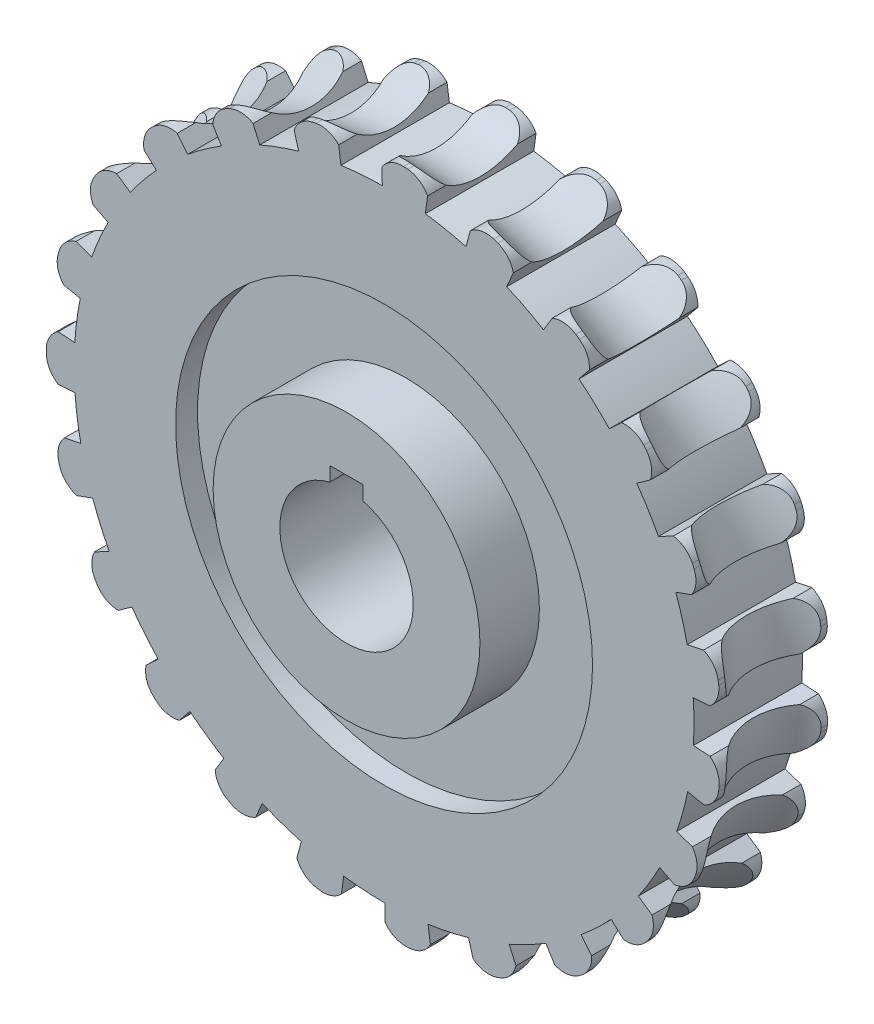
SolidWorks part; units mm, degrees
ref_plane "Front Plane" through (0, 0, 0) normal (0, 0, 1) x (1, 0, 0)
ref_plane "Top Plane" through (0, 0, 0) normal (0, 1, 0) x (1, 0, 0)
ref_plane "Right Plane" through (0, 0, 0) normal (1, 0, 0) x (0, 0, -1)
sketch "Sketch2" plane through (0, 0, 0) normal (0, 0, 1) x (1, 0, 0)
  line L9 (-6, 28.3779) -> (6, 28.3779)
  line L10 (-6, 28.3779) -> (-6, 23.2379)
  line L12 (6, 28.3779) -> (6, 23.2379)
  circle A1 centre (0, 0) radius 121.5
  arc A2 (-6, 23.2379) -> (6, 23.2379) centre (0, 0) ccw
  point P4 (0, 23.2379)
  dimension "D4" = 243
  dimension "D5" = 48
  dimension "D2" = 12
extrude "Boss-Extrude1" add sketch "Sketch2" along normal mid plane 39
sketch "Sketch3" plane through (0, 0, 0) normal (0, 0, 1) x (1, 0, 0)
  line L0 (6, 23.2379) -> (6, 28.3779) construction
  line L1 (6, 28.3779) -> (-6, 28.3779) construction
  line L2 (-6, 28.3779) -> (-6, 23.2379) construction
  line L3 (6, 23.2379) -> (6, 28.3779)
  line L4 (6, 28.3779) -> (-6, 28.3779)
  line L5 (-6, 28.3779) -> (-6, 23.2379)
  circle A0 centre (0, 0) radius 48
  arc A1 (-6, 23.2379) -> (6, 23.2379) centre (0, 0) ccw construction
  arc A2 (-6, 23.2379) -> (6, 23.2379) centre (0, 0) ccw
  dimension "D1" = 96
extrude "Boss-Extrude3" add sketch "Sketch3" along normal mid plane 66
sketch "Sketch4" plane through (0, 0, 19.5) normal (0, 0, 1) x (1, 0, 0)
  circle A0 centre (0, 0) radius 75
  circle A1 centre (0, 0) radius 48 construction
  circle A2 centre (0, 0) radius 48
extrude "Cut-Extrude2" cut sketch "Sketch4" against normal blind 7.89
mirror "Mirror1" about plane through (0, 0, 0) normal (0, 0, 1) of "Cut-Extrude2"
sketch "Sketch6" plane through (0, 0, 0) normal (1, 0, 0) x (0, 0, -1)
  line L0 (0, 0) -> (0, -136) construction
  line L1 (0, 0) -> (197.1209, 0) construction
  circle A0 centre (0, -136) radius 22.5
  dimension "D2" = 45
  dimension "D1" = 136
revolve "Cut-Revolve1" cut sketch "Sketch6" angle 360 about L1 other way angle 360
sketch "Sketch7" plane through (0, 0, 0) normal (0, 0, 1) x (1, 0, 0)
  line L2 (14.8615, 110.5051) -> (15.6612, 116.4516) construction
  line L4 (15.6612, 116.4516) -> (14.8615, 110.5051)
  line L5 (31.043, 113.3251) -> (29.4578, 107.5383)
  arc A3 (8.1153, 121.2287) -> (15.6612, 116.4516) centre (7.7086, 112.2379) cw
  arc A5 (14.8615, 110.5051) -> (29.4578, 107.5383) centre (0, 0) cw
  arc A6 (39.855, 114.7773) -> (31.043, 113.3251) centre (36.7196, 106.3411) ccw
  arc A8 (8.1153, 121.2287) -> (39.855, 114.7773) centre (0, 0) cw
  arc A9 (29.4578, 107.5383) -> (14.8615, 110.5051) centre (0, 0) ccw construction
  arc A11 (39.855, 114.7773) -> (8.1153, 121.2287) centre (0, 0) ccw construction
  dimension "D4" = 9
extrude "Cut-Extrude3" cut sketch "Sketch7" against normal through all both and the other way through all contours A8 A3 L4 A5 L5 A6 region at (23.2766, 114.5171, 0)
pattern_circular "CirPattern2" count 23 over 360 about axis through (0, 0, 19.5) along (0, 0, 1) of "Cut-Extrude3"
